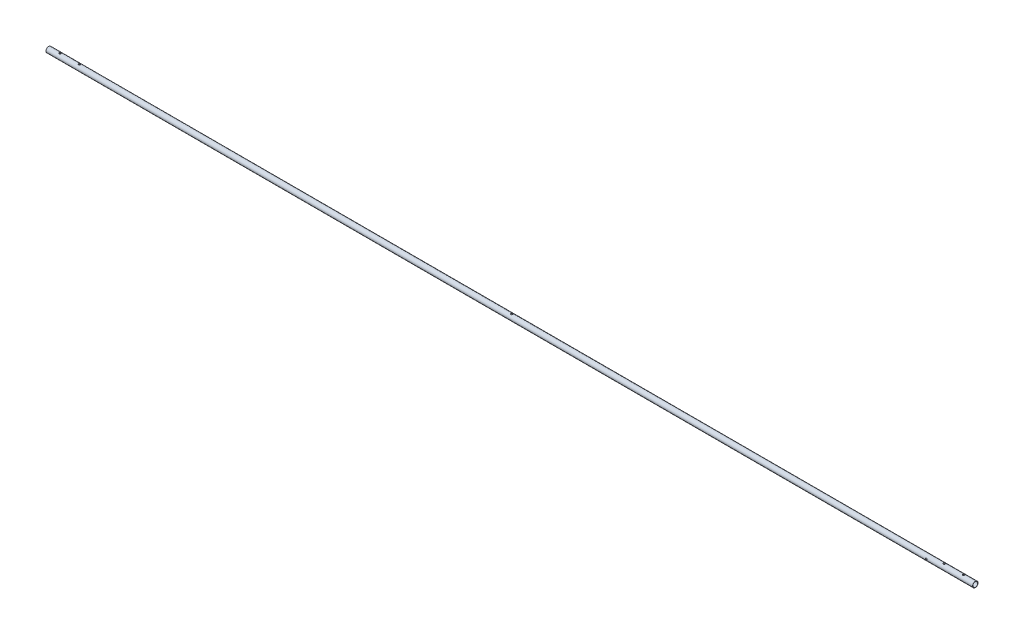
SolidWorks part; units mm, degrees
material "Galvanized Steel"
ref_plane "Front Plane" through (0, 0, 0) normal (0, 0, 1) x (1, 0, 0)
ref_plane "Top Plane" through (0, 0, 0) normal (0, 1, 0) x (1, 0, 0)
ref_plane "Right Plane" through (0, 0, 0) normal (1, 0, 0) x (0, 0, -1)
sketch "Sketch1" plane through (0, 0, 0) normal (1, 0, 0) x (0, 0, -1)
  circle A0 centre (0, 0) radius 7.8994
  circle A1 centre (0, 0) radius 8.9662
  dimension "D1" = 15.7988
  dimension "D2" = 17.9324
extrude "Boss-Extrude1" add sketch "Sketch1" along normal blind 3048
sketch "Sketch2" plane through (0, 0, 0) normal (0, 1, 0) x (1, 0, 0)
  line L0 (0, 8.9662) -> (0, -8.9662) construction
  line L1 (3048, -8.9662) -> (3048, 8.9662) construction
  circle A0 centre (38.1, 0) radius 3.175
  circle A1 centre (3009.9, 0) radius 3.175
  circle A2 centre (101.6, 0) radius 3.175
  circle A3 centre (2946.4, 0) radius 3.175
  dimension "D1" = 6.35
  dimension "D3" = 6.35
  dimension "D5" = 6.35
  dimension "D7" = 6.35
  dimension "D2" = 38.1
  dimension "D4" = 38.1
  dimension "D6" = 101.6
  dimension "D8" = 101.6
sketch "Sketch3" plane through (0, 0, 0) normal (0, 1, 0) x (1, 0, 0)
  line L0 (0, 8.9662) -> (0, -8.9662) construction
  circle A0 centre (1524, 0) radius 3.175
  dimension "D1" = 6.35
  dimension "D2" = 1524
extrude "Cut-Extrude2" cut sketch "Sketch3" against normal through all and the other way through all
extrude "Cut-Extrude5" cut sketch "Sketch2" against normal through all and the other way through all
sketch "Sketch4" plane through (0, 0, 0) normal (0, 0, 1) x (1, 0, 0)
  line L1 (3048, -8.9662) -> (3048, 8.9662) construction
  circle A0 centre (2895.6, 0) radius 3.175
  dimension "D1" = 152.4
extrude "Cut-Extrude6" cut sketch "Sketch4" against normal through all and the other way through all
